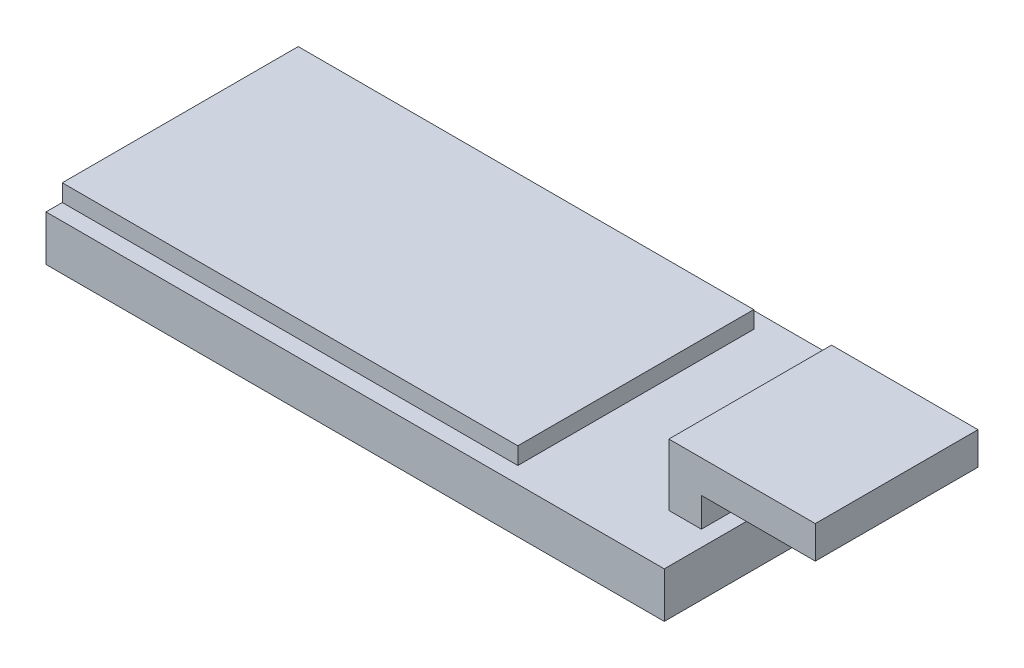
SolidWorks part; units mm, degrees
ref_plane "前视基准面" through (0, 0, 0) normal (0, 0, 1) x (1, 0, 0)
ref_plane "上视基准面" through (0, 0, 0) normal (0, 1, 0) x (1, 0, 0)
ref_plane "右视基准面" through (0, 0, 0) normal (1, 0, 0) x (0, 0, -1)
other "Configuration Table"
sketch "Sketch1" plane through (0, 0, 0) normal (0, 1, 0) x (1, 0, 0)
  line L1 (0, 8.25) -> (38, 8.25)
  line L2 (0, 8.25) -> (0, -8.25)
  line L3 (0, -8.25) -> (38, -8.25)
  line L4 (38, 8.25) -> (38, -8.25)
  line L5 (0, 7.25) -> (28, 7.25)
  line L6 (0, 7.25) -> (0, -7.25)
  line L7 (0, -7.25) -> (28, -7.25)
  line L8 (28, 7.25) -> (28, -7.25)
  point P4 (0, 0)
  point P10 (28, 0)
  dimension "D1" = 38
  dimension "D2" = 16.5
  dimension "D3" = 1
  dimension "D4" = 28
extrude "Boss-Extrude1" add sketch "Sketch1" along normal blind 2.4 and the other way blind 0.4 contours L5 L8 L7 L2 L3 L4 L1 | L8 L5 L2 L7 region at (28.1855, 0, 0) region at (14, 0, 0)
extrude "Boss-Extrude2" add sketch "Sketch1<3>" along normal blind 1.05 from surface contours L8 L5 L2 L7 region at (14, 0, 0) starting at face at (19, 2.4, 0)
sketch "Sketch1<3>" plane through (0, 0, 0) normal (0, 1, 0) x (1, 0, 0) same geometry as "Sketch1"
sketch "Sketch2" plane through (0, 0, 0) normal (0, 0, 1) x (1, 0, 0)
  line L0 (37.0321, -1) -> (35.0321, -1)
  line L1 (35.0321, -1) -> (35.0321, 6.2)
  line L2 (35.0321, 6.2) -> (44.0321, 6.2)
  line L3 (44.0321, 6.2) -> (44.0321, 4.2)
  line L4 (44.0321, 4.2) -> (37.0321, 4.2)
  line L5 (37.0321, 4.2) -> (37.0321, -1)
  dimension "D1" = 2
  dimension "D2" = 9
  dimension "D3" = 2
  dimension "D4" = 1
  dimension "D5" = 4.2
extrude "Boss-Extrude3" add sketch "Sketch2" along normal mid plane 10
